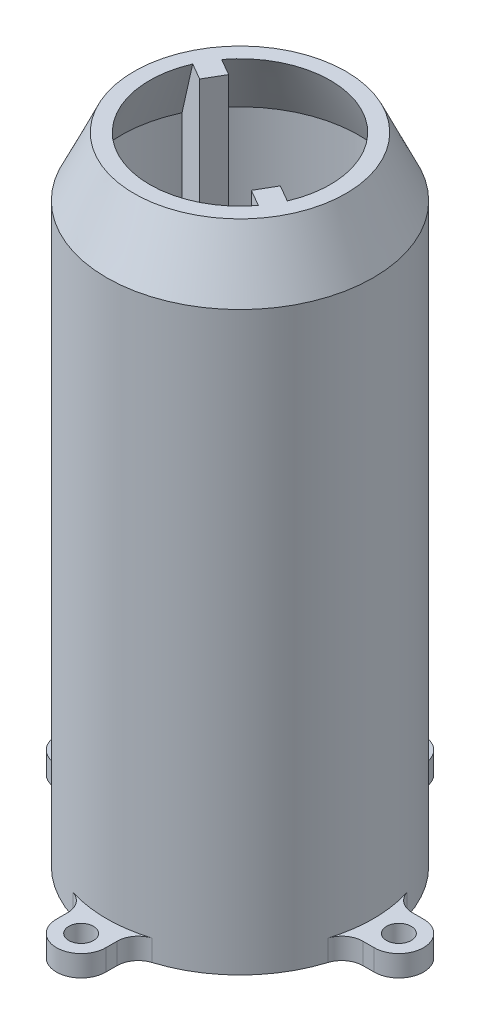
SolidWorks part; units mm, degrees
ref_plane "Front Plane" through (0, 0, 0) normal (0, 0, 1) x (1, 0, 0)
ref_plane "Top Plane" through (0, 0, 0) normal (0, 1, 0) x (1, 0, 0)
ref_plane "Right Plane" through (0, 0, 0) normal (1, 0, 0) x (0, 0, -1)
sketch "Sketch1" plane through (0, 0, 0) normal (1, 0, 0) x (0, 0, -1)
  line L0 (-15, 90) -> (-18.9, 81.6364)
  line L1 (-18.9, 81.6364) -> (-18.9, 3)
  line L2 (0, -1110.9691) -> (0, 54437.4866) construction
  line L3 (-15, 90) -> (-12.7932, 90)
  line L4 (-12.7932, 90) -> (-16.9, 81.193)
  line L5 (-16.9, 81.193) -> (-16.9, 0)
  line L6 (-16.9, 0) -> (-17.6, 0)
  line L7 (-1000, 0) -> (49000, 0) construction
  line L8 (-18.9, 3) -> (-31.9, 3)
  line L9 (-31.9, 3) -> (-31.9, 0)
  line L12 (-31.9, 0) -> (-16.9, 0)
  dimension "D1" = 2
  dimension "D2" = 2
  dimension "D3" = 18.9
  dimension "D4" = 15
  dimension "D5" = 65
  dimension "D6" = 90
  dimension "D7" = 8.3636
  dimension "D8" = 12.7932
  dimension "D9" = 13
  dimension "D10" = 3
revolve "Revolve1" add sketch "Sketch1" angle 360 about L2
sketch "Sketch2" plane through (0, 0, 0) normal (0, -1, 0) x (1, 0, 0)
  line L0 (-1000, 0) -> (49000, 0) construction
  line L1 (0, -1000) -> (0, 49000) construction
  circle A0 centre (0, 22.5) radius 1.75
  circle A1 centre (0, -22.5) radius 1.75
  circle A2 centre (-22.5, 0) radius 1.75
  circle A3 centre (22.5, 0) radius 1.75
  circle A4 centre (0, 0) radius 22.5 construction
  dimension "D2" = 3.5
  dimension "D3" = 45
extrude "Cut-Extrude1" cut sketch "Sketch2" against normal blind 10
sketch "Sketch4" plane through (0, 3, 0) normal (0, 1, 0) x (1, 0, 0)
  line L0 (-3.5, 22.5) -> (-3.5, 17.2485)
  line L1 (3.5, 22.5) -> (3.5, 17.2485)
  line L2 (22.5, 3.5) -> (17.2485, 3.5)
  line L3 (22.5, -3.5) -> (17.2485, -3.5)
  line L4 (3.5, -22.5) -> (3.5, -17.2485)
  line L5 (-3.5, -22.5) -> (-3.5, -17.2485)
  line L6 (-22.5, -3.5) -> (-17.2485, -3.5)
  line L7 (-22.5, 3.5) -> (-17.2485, 3.5)
  circle A1 centre (0, 0) radius 36.8375
  arc A4 (22.5, -3.5) -> (22.5, 3.5) centre (22.5, 0) ccw
  arc A6 (-3.5, -22.5) -> (3.5, -22.5) centre (0, -22.5) ccw
  arc A9 (-22.5, 3.5) -> (-22.5, -3.5) centre (-22.5, 0) ccw
  circle A10 centre (0, 0) radius 17.6
  arc A11 (3.5, 22.5) -> (-3.5, 22.5) centre (0, 22.5) ccw
  point P27 (0, 0)
  point P39 (0, 0)
  point P58 (0, 0)
  circle M8 centre (0, 0) radius 31.9
  circle M9 centre (0, 0) radius 18.9
  dimension "D1" = 7
  dimension "D2" = 4
extrude "Cut-Extrude2" cut sketch "Sketch4" against normal through all contours A11 L1 L2 A4 L3 L4 A6 L5 L6 A9 L7 L0 M8 M9 | A1 M8
fillet "Fillet1" radius 3 8 edges at (-3.5, 1.5, 18.5731) (-18.5731, 1.5, 3.5) (-18.5731, 1.5, -3.5) (-3.5, 1.5, -18.5731) (3.5, 1.5, -18.5731) (18.5731, 1.5, -3.5) (18.5731, 1.5, 3.5) (3.5, 1.5, 18.5731)
sketch "Sketch5" plane through (0, 0, 0) normal (0, -1, 0) x (1, 0, 0)
  line L0 (0, 0) -> (50.1842, 0) construction
  line L1 (14.8385, 10.299) -> (16.3385, 7.701)
  line L2 (14.8385, 10.299) -> (7.9103, 6.299)
  line L3 (7.9103, 6.299) -> (9.4103, 3.701)
  line L4 (16.3385, 7.701) -> (9.4103, 3.701)
  line L5 (0, 0) -> (25.2331, 14.5684) construction
  line L10 (-14.8385, -10.299) -> (-16.3385, -7.701)
  line L11 (-14.8385, -10.299) -> (-7.9103, -6.299)
  line L12 (-7.9103, -6.299) -> (-9.4103, -3.701)
  line L13 (-16.3385, -7.701) -> (-9.4103, -3.701)
  point P14 (0, 0)
  dimension "D1" = 3
  dimension "D2" = 10
  dimension "D3" = 8
  dimension "D5" = 30
  dimension "D4" = 2
extrude "Boss-Extrude1" add sketch "Sketch5" against normal up to surface (78.7003 mm away) up to face at (0, 81.193, -16.9)
ref_plane "Plane1" through (0, 90, 0) normal (0, 1, 0) x (1, 0, 0)
other "SurfaceCut2" flip cut yes
equation "\"d_mount1_holes\"= 45"
equation "\"D3@Sketch2\"=\"d_mount1_holes\""
